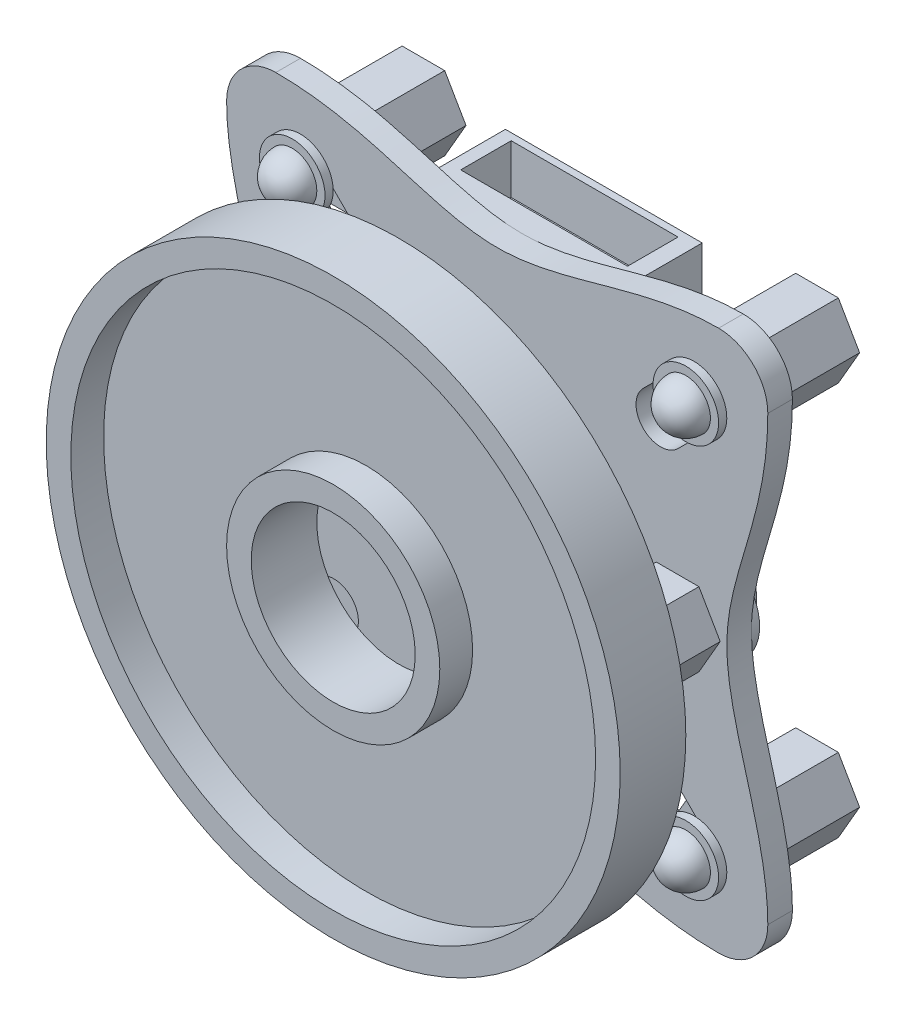
SolidWorks part; units mm, degrees
note: The reader was unsure of these and kept them because the rebuilt part matched: shared geometry of "草图1<3>".
ref_plane "前视基准面" through (0, 0, 0) normal (0, 0, 1) x (1, 0, 0)
ref_plane "上视基准面" through (0, 0, 0) normal (0, 1, 0) x (1, 0, 0)
ref_plane "右视基准面" through (0, 0, 0) normal (1, 0, 0) x (0, 0, -1)
other "Configuration Table"
sketch "草图1" plane through (0, 0, 0) normal (0, 0, 1) x (1, 0, 0)
  line L0 (-17.5, 0) -> (17.5, 0) construction
  line L2 (-13.5981, 0) -> (-12.299, -2.25)
  line L3 (-12.299, -2.25) -> (-9.701, -2.25)
  line L4 (-9.701, -2.25) -> (-8.4019, 0)
  line L5 (-8.4019, 0) -> (-9.701, 2.25)
  line L6 (-9.701, 2.25) -> (-12.299, 2.25)
  line L7 (-12.299, 2.25) -> (-13.5981, 0)
  line L8 (8.4019, 0) -> (9.701, -2.25)
  line L9 (9.701, -2.25) -> (12.299, -2.25)
  line L10 (12.299, -2.25) -> (13.5981, 0)
  line L11 (13.5981, 0) -> (12.299, 2.25)
  line L12 (12.299, 2.25) -> (9.701, 2.25)
  line L13 (9.701, 2.25) -> (8.4019, 0)
  circle A0 centre (0, 0) radius 17.5
  circle A1 centre (0, 0) radius 5
  circle A2 centre (0, 0) radius 11 construction
  circle A3 centre (-11, 0) radius 2.25 construction
  circle A4 centre (11, 0) radius 2.25 construction
  dimension "D1" = 35
  dimension "D2" = 10
  dimension "D3" = 22
  dimension "D4" = 4.5
  dimension "D5" = 4.5
extrude "凸台-拉伸1" add sketch "草图1" along normal blind 4 contours A0 A1 L7 L6 L5 L4 L3 L2 L13 L12 L11 L10 L9 L8 | L6 L7 L2 L3 L4 L5 | L12 L13 L8 L9 L10 L11
extrude "凸台-拉伸2" add sketch "草图1<3>" against normal blind 6 contours L6 L7 L2 L3 L4 L5 | L12 L13 L8 L9 L10 L11
sketch "草图1<3>" plane through (0, 0, 0) normal (0, 0, 1) x (1, 0, 0) same geometry as "草图1"
sketch "草图3" plane through (0, 0, -6) normal (0, 0, -1) x (-1, 0, 0)
  circle A0 centre (-11, 0) radius 3
  circle A1 centre (11, 0) radius 3
  dimension "D1" = 6
  dimension "D2" = 6
extrude "凸台-拉伸4" add sketch "草图3" along normal blind 2
sketch "草图2" plane through (0, 0, 0) normal (0, 0, -1) x (-1, 0, 0)
  line L0 (-12.0858, 12.0858) -> (-9.9645, 9.9645) construction
  line L1 (-16.5, 16.5) -> (16.5, 16.5) construction
  line L2 (-16.5, 16.5) -> (-16.5, -16.5) construction
  line L3 (-16.5, -16.5) -> (16.5, -16.5) construction
  line L4 (16.5, 16.5) -> (16.5, -16.5) construction
  line L5 (-16.5, 16.5) -> (16.5, -16.5) construction
  line L6 (-16.5, -16.5) -> (16.5, 16.5) construction
  line L7 (-14, 14) -> (14, 14) construction
  line L8 (-14, 14) -> (-14, -14) construction
  line L9 (-14, -14) -> (14, -14) construction
  line L10 (14, 14) -> (14, -14) construction
  line L11 (-14, 14) -> (14, -14) construction
  line L12 (-14, -14) -> (14, 14) construction
  line L13 (-11.0251, 13.1464) -> (-8.9038, 11.0251)
  line L14 (-13.1464, 11.0251) -> (-11.0251, 8.9038)
  line L15 (9.9645, 9.9645) -> (12.0858, 12.0858) construction
  line L16 (8.9038, 11.0251) -> (11.0251, 13.1464)
  line L17 (11.0251, 8.9038) -> (13.1464, 11.0251)
  line L18 (12.0858, -12.0858) -> (9.9645, -9.9645) construction
  line L19 (11.0251, -13.1464) -> (8.9038, -11.0251)
  line L20 (13.1464, -11.0251) -> (11.0251, -8.9038)
  line L21 (-12.0858, -12.0858) -> (-9.9645, -9.9645) construction
  line L22 (-13.1464, -11.0251) -> (-11.0251, -8.9038)
  line L23 (-11.0251, -13.1464) -> (-8.9038, -11.0251)
  circle A0 centre (-13.5, 13.5) radius 3
  circle A1 centre (13.5, 13.5) radius 3
  circle A2 centre (13.5, -13.5) radius 3
  circle A3 centre (-13.5, -13.5) radius 3
  arc A4 (-11.0251, 13.1464) -> (-13.1464, 11.0251) centre (-12.0858, 12.0858) ccw
  arc A5 (-11.0251, 8.9038) -> (-8.9038, 11.0251) centre (-9.9645, 9.9645) ccw
  arc A6 (8.9038, 11.0251) -> (11.0251, 8.9038) centre (9.9645, 9.9645) ccw
  arc A7 (13.1464, 11.0251) -> (11.0251, 13.1464) centre (12.0858, 12.0858) ccw
  arc A8 (11.0251, -13.1464) -> (13.1464, -11.0251) centre (12.0858, -12.0858) ccw
  arc A9 (11.0251, -8.9038) -> (8.9038, -11.0251) centre (9.9645, -9.9645) ccw
  arc A10 (-13.1464, -11.0251) -> (-11.0251, -13.1464) centre (-12.0858, -12.0858) ccw
  arc A11 (-8.9038, -11.0251) -> (-11.0251, -8.9038) centre (-9.9645, -9.9645) ccw
  spline S0 degree 3 poles (-13.5, 16.5) (-8.7013, 16.5) (0.5221, 11.5) (7.6572, 16.5) (13.5, 16.5) knots 0 0 0 0 0.5 1 1 1 1
  spline S1 degree 3 poles (16.5, 13.5) (16.5, 8.7013) (11.5, -0.5221) (16.5, -7.6572) (16.5, -13.5) knots 0 0 0 0 0.5 1 1 1 1
  spline S2 degree 3 poles (-13.5, -16.5) (-7.6572, -16.5) (-0.5221, -11.5) (8.7013, -16.5) (13.5, -16.5) knots 0 0 0 0 0.5 1 1 1 1
  spline S3 degree 3 poles (-16.5, 13.5) (-16.5, 7.6572) (-11.5, 0.5221) (-16.5, -8.7013) (-16.5, -13.5) knots 0 0 0 0 0.5 1 1 1 1
  point P0 (0, 0)
  point P6 (0, 0)
  point P33 (-11.0251, 11.0251)
  point P38 (11.0251, 11.0251)
  point P45 (11.0251, -11.0251)
  point P52 (-11.0251, -11.0251)
  dimension "D5" = 6
  dimension "D6" = 6
  dimension "D7" = 6
  dimension "D8" = 6
  dimension "D9" = 1.5
  dimension "D10" = 1.5
  dimension "D11" = 1.5
  dimension "D12" = 1.5
  dimension "D17" = 2
  dimension "D18" = 2
  dimension "D19" = 2
  dimension "D20" = 2
  dimension "D1" = 33
  dimension "D2" = 33
  dimension "D3" = 28
  dimension "D4" = 28
  dimension "D13" = 3
  dimension "D14" = 3
  dimension "D15" = 3
  dimension "D16" = 3
extrude "凸台-拉伸3" add sketch "草图2" along normal blind 1.5 from offset 6
sketch "草图4" plane through (0, 0, -8) normal (0, 0, -1) x (-1, 0, 0)
  circle A0 centre (-11, 0) radius 2
  circle A1 centre (11, 0) radius 2
  dimension "D1" = 4
  dimension "D2" = 4
extrude "凸台-拉伸5" add sketch "草图4" along normal blind 2
fillet "圆角1" radius 2 2 edges at (-13, 0, -10) (9, 0, -10)
sketch "草图5" plane through (0, 0, -7.5) normal (0, 0, -1) x (-1, 0, 0)
  line L0 (0, 17.5) -> (0, -17.5) construction
  line L2 (-6, 14) -> (6, 14)
  line L3 (-6, 14) -> (-6, 7.5)
  line L4 (-6, 7.5) -> (6, 7.5)
  line L5 (6, 14) -> (6, 7.5)
  line L6 (-6, 14) -> (6, 7.5) construction
  line L7 (-6, 7.5) -> (6, 14) construction
  line L8 (-6, -7.5) -> (6, -7.5)
  line L9 (-6, -7.5) -> (-6, -14)
  line L10 (-6, -14) -> (6, -14)
  line L11 (6, -7.5) -> (6, -14)
  line L12 (-6, -7.5) -> (6, -14) construction
  line L13 (-6, -14) -> (6, -7.5) construction
  circle A0 centre (0, 0) radius 17.5 construction
  point P5 (0, 10.75)
  point P10 (0, -10.75)
  dimension "D1" = 6.5
  dimension "D2" = 12
  dimension "D3" = 6.5
  dimension "D4" = 12
  dimension "D5" = 7.5
  dimension "D6" = 7.5
extrude "凸台-拉伸6" add sketch "草图5" along normal blind 5
sketch "草图6" plane through (0, -14, 0) normal (0, -1, 0) x (1, 0, 0)
  line L1 (-4.9769, -8.5774) -> (4.928, -8.5774)
  line L2 (-4.9769, -8.5774) -> (-4.9769, -12.0013)
  line L3 (-4.9769, -12.0013) -> (4.928, -12.0013)
  line L4 (4.928, -8.5774) -> (4.928, -12.0013)
extrude "切除-拉伸1" cut sketch "草图6" against normal blind 3
sketch "草图7" plane through (0, 14, 0) normal (0, 1, 0) x (1, 0, 0)
  line L2 (-5.2214, 12.0747) -> (4.9524, 12.0747)
  line L3 (-5.2214, 12.0747) -> (-5.2214, 8.9932)
  line L4 (-5.2214, 8.9932) -> (4.9524, 8.9932)
  line L5 (4.9524, 12.0747) -> (4.9524, 8.9932)
extrude "切除-拉伸2" cut sketch "草图7" against normal blind 3
sketch "草图8" plane through (0, 0, -7.5) normal (0, 0, -1) x (-1, 0, 0)
  line L1 (-14.5981, 12) -> (-13.299, 9.75)
  line L2 (-13.299, 9.75) -> (-10.701, 9.75)
  line L3 (-10.701, 9.75) -> (-9.4019, 12)
  line L4 (-9.4019, 12) -> (-10.701, 14.25)
  line L5 (-10.701, 14.25) -> (-13.299, 14.25)
  line L6 (-13.299, 14.25) -> (-14.5981, 12)
  line L7 (14.5981, 12) -> (13.299, 14.25)
  line L8 (13.299, 14.25) -> (10.701, 14.25)
  line L9 (10.701, 14.25) -> (9.4019, 12)
  line L10 (9.4019, 12) -> (10.701, 9.75)
  line L11 (10.701, 9.75) -> (13.299, 9.75)
  line L12 (13.299, 9.75) -> (14.5981, 12)
  line L13 (14.5981, -12) -> (13.299, -9.75)
  line L14 (13.299, -9.75) -> (10.701, -9.75)
  line L15 (10.701, -9.75) -> (9.4019, -12)
  line L16 (9.4019, -12) -> (10.701, -14.25)
  line L17 (10.701, -14.25) -> (13.299, -14.25)
  line L18 (13.299, -14.25) -> (14.5981, -12)
  line L19 (-14.5981, -12) -> (-13.299, -14.25)
  line L20 (-13.299, -14.25) -> (-10.701, -14.25)
  line L21 (-10.701, -14.25) -> (-9.4019, -12)
  line L22 (-9.4019, -12) -> (-10.701, -9.75)
  line L23 (-10.701, -9.75) -> (-13.299, -9.75)
  line L24 (-13.299, -9.75) -> (-14.5981, -12)
  line L25 (-12, 12) -> (12, 12)
  line L26 (-12, 12) -> (-12, -12)
  line L27 (-12, -12) -> (12, -12)
  line L28 (12, 12) -> (12, -12)
  line L29 (-12, 12) -> (12, -12) construction
  line L30 (-12, -12) -> (12, 12) construction
  circle A0 centre (-12, 12) radius 2.25 construction
  circle A1 centre (12, 12) radius 2.25 construction
  circle A2 centre (12, -12) radius 2.25 construction
  circle A3 centre (-12, -12) radius 2.25 construction
  point P28 (0, 0)
  arc M3 (-13.1464, 11.0251) -> (-11.0251, 13.1464) centre (-12.0858, 12.0858) cw
  line M12 (8.9038, 11.0251) -> (11.0251, 13.1464)
  line M69 (-11.0251, 13.1464) -> (-8.9038, 11.0251)
  line M71 (-11.0251, 8.9038) -> (-13.1464, 11.0251)
  arc M72 (-11.0251, -13.1464) -> (-13.1464, -11.0251) centre (-12.0858, -12.0858) cw
  line M73 (-13.1464, -11.0251) -> (-11.0251, -8.9038)
  line M75 (-8.9038, -11.0251) -> (-11.0251, -13.1464)
  arc M76 (11.0251, 13.1464) -> (13.1464, 11.0251) centre (12.0858, 12.0858) cw
  line M77 (13.1464, 11.0251) -> (11.0251, 8.9038)
  line M79 (11.0251, -13.1464) -> (8.9038, -11.0251)
  arc M82 (13.1464, -11.0251) -> (11.0251, -13.1464) centre (12.0858, -12.0858) cw
  line M88 (11.0251, -8.9038) -> (13.1464, -11.0251)
  dimension "D1" = 4.5
  dimension "D2" = 4.5
  dimension "D3" = 4.5
  dimension "D4" = 4.5
  dimension "D5" = 24
  dimension "D6" = 24
extrude "凸台-拉伸7" add sketch "草图8" along normal blind 6 contours L26 L25 L4 L2 M69 M3 M71 | L5 L6 L1 L2 L4 M71 M3 M69 | L25 L26 L2 L3 | L25 L28 L11 L9 M77 M76 M12 | L11 L12 L7 L8 L9 M12 M76 M77 | L28 L25 L10 L11 | L28 L14 L15 L27 | L14 L28 L27 L16 M79 M82 M88 | L17 L18 L13 L14 L16 M88 M82 M79 | L27 L26 L23 L21 M73 M72 M75 | L26 L27 L22 L23 | L23 L24 L19 L20 L21 M75 M72 M73 | L15 L27 M79 | L25 L10 M12 | L28 L11 M77 | L25 L3 M69 | L26 L2 M71 | L27 L22 M75 | L23 L26 M73 | L28 L14 M88
sketch "草图9" plane through (0, 0, -6) normal (0, 0, 1) x (1, 0, 0)
  line L1 (-12, 12) -> (12, 12)
  line L2 (-12, 12) -> (-12, -12)
  line L3 (-12, -12) -> (12, -12)
  line L4 (12, 12) -> (12, -12)
  line L5 (-12, 12) -> (12, -12) construction
  line L6 (-12, -12) -> (12, 12) construction
  circle A0 centre (12, 12) radius 1.25
  circle A1 centre (-12, 12) radius 1.25
  circle A2 centre (-12, -12) radius 1.25
  circle A3 centre (12, -12) radius 1.25
  point P12 (0, 0)
  dimension "D1" = 2.5
  dimension "D2" = 2.5
  dimension "D3" = 2.5
  dimension "D4" = 2.5
  dimension "D5" = 24
  dimension "D6" = 24
extrude "凸台-拉伸8" add sketch "草图9" against normal blind 1.5 contours L1 A1 L2 | L2 A1 L1 | L4 A0 L1 | L1 A0 L4 | L2 A2 L3 | L3 A2 L2 | L3 A3 L4 | L4 A3 L3
sketch "草图10" plane through (0, 0, -6) normal (0, 0, 1) x (1, 0, 0)
  circle A0 centre (-12, 12) radius 2
  circle A1 centre (12, 12) radius 2
  circle A2 centre (12, -12) radius 2
  circle A3 centre (-12, -12) radius 2
  dimension "D1" = 4
  dimension "D2" = 4
  dimension "D3" = 4
  dimension "D4" = 4
extrude "凸台-拉伸9" add sketch "草图10" along normal blind 0.5
sketch "草图11" plane through (0, 0, -5.5) normal (0, 0, 1) x (1, 0, 0)
  circle A0 centre (-12, 12) radius 1.5
  circle A1 centre (12, 12) radius 1.5
  circle A2 centre (12, -12) radius 1.5
  circle A3 centre (-12, -12) radius 1.5
  dimension "D1" = 3
  dimension "D2" = 3
  dimension "D3" = 3
  dimension "D4" = 3
extrude "凸台-拉伸10" add sketch "草图11" along normal blind 1.5
fillet "圆角2" radius 1.5 4 edges at (13.5, 12, -4) (13.5, -12, -4) (-10.5, -12, -4) (-10.5, 12, -4)
sketch "草图12" plane through (0, 0, -12.5) normal (0, 0, -1) x (-1, 0, 0)
  text T0 "接口位置" font "汉仪长仿宋体" height 1.5
extrude "切除-拉伸3" cut sketch "草图12" against normal blind 0.1
sketch "草图13" plane through (0, 0, -12.5) normal (0, 0, -1) x (-1, 0, 0)
  text T0 "接口位置2" font "汉仪长仿宋体" height 1.5
extrude "切除-拉伸4" cut sketch "草图13" against normal blind 0.1
sketch "草图14" plane through (0, 0, 4) normal (0, 0, 1) x (1, 0, 0)
  circle A0 centre (0, 0) radius 6.5
  circle A1 centre (0, 0) radius 16
  dimension "D1" = 32
  dimension "D2" = 13
extrude "切除-拉伸5" cut sketch "草图14" against normal blind 2
hole_wizard "M2.5 螺纹孔的螺纹孔钻头1" positions "草图16" profile "草图17" hole size "M2.5" standard "GB"
sketch "草图16" plane through (0, 0, -13.5) normal (0, 0, -1) x (-1, 0, 0)
  point P0 (-12, 12)
  point P2 (12, 12)
  point P4 (12, -12)
  point P6 (-12, -12)
sketch "草图17" plane through (12, 12, -13.5) normal (1, 0, 0) x (0, 1, 0)
  line L0 (0, 0) -> (0, 3.6159)
  line L1 (0, 3.6159) -> (1.025, 3)
  line L2 (1.025, 3) -> (1.025, 0)
  line L5 (1.025, 0) -> (0, 0)
  line L10 (0, 3.6159) -> (-1.025, 3) construction
  line L11 (0, -6.35) -> (0, 107.95) construction
  dimension "孔直径" = 2.05
  dimension "孔深度" = 3
  dimension "导头角度" = 118
cosmetic thread "装饰螺纹线1" parameters "D2"=2.5
cosmetic thread "装饰螺纹线2" parameters "D2"=2.5
cosmetic thread "装饰螺纹线3" parameters "D2"=2.5
cosmetic thread "装饰螺纹线4" parameters "D2"=2.5
